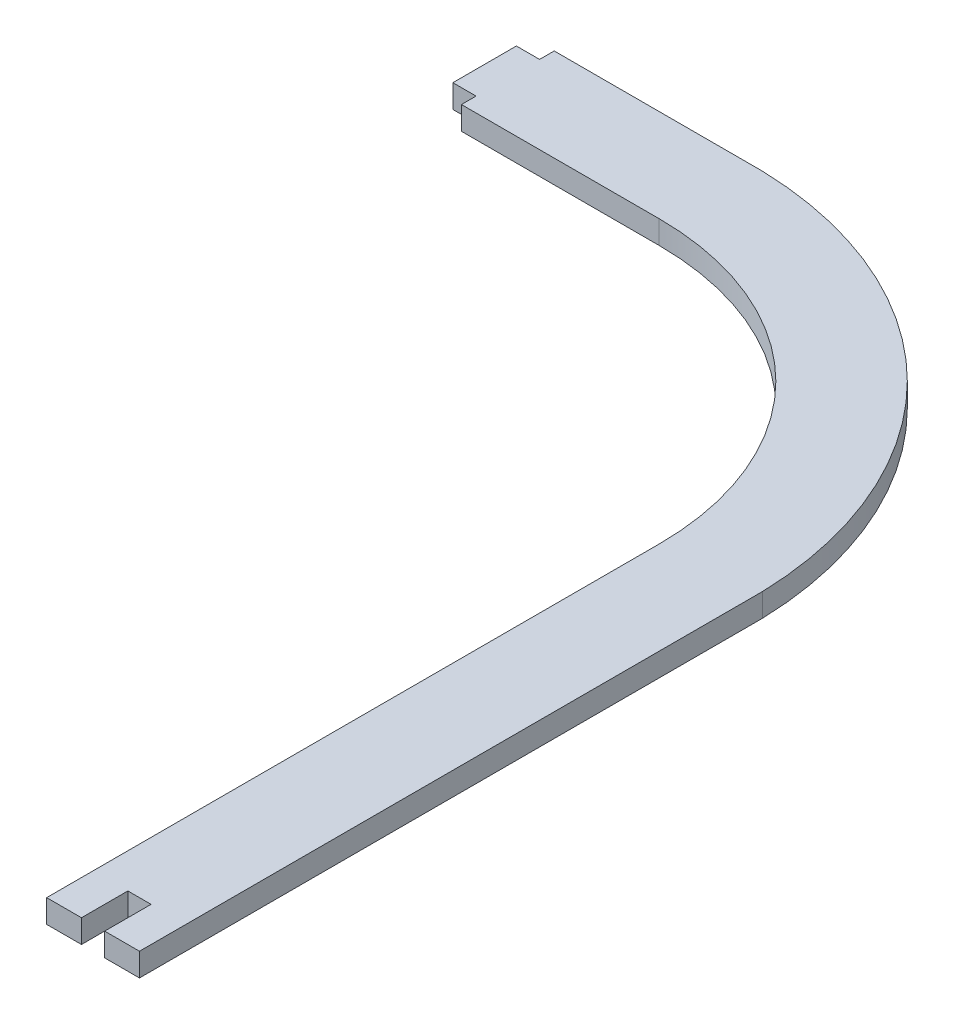
SolidWorks part; units mm, degrees
ref_plane "Alzado" through (0, 0, 0) normal (0, 0, 1) x (1, 0, 0)
ref_plane "Planta" through (0, 0, 0) normal (0, 1, 0) x (1, 0, 0)
ref_plane "Vista lateral" through (0, 0, 0) normal (1, 0, 0) x (0, 0, -1)
sketch "Croquis1" plane through (0, 0, 0) normal (0, 1, 0) x (1, 0, 0)
  line L0 (0, 0) -> (0, 8)
  line L1 (0, 8) -> (3, 8)
  line L2 (3, -2.107) -> (3, -0.2139)
  line L3 (3, 9.893) -> (7.3583, 9.893)
  line L4 (3, 3.893) -> (72.5, 3.893) construction
  line L5 (72.5, 3.893) -> (72.5, -105.737) construction
  line L6 (3, -2.107) -> (7.3583, -2.107)
  line L7 (0, -0.2139) -> (3, -0.2139)
  line L8 (0, 7.7861) -> (0, -0.2139)
  line L9 (3, 8) -> (3, 9.893)
  line L10 (72.5, -111.737) -> (72.5, -117.737)
  line L11 (72.5, -105.737) -> (72.5, -111.737) construction
  line L12 (72.5, -111.737) -> (69.5, -111.737)
  line L13 (69.5, -111.737) -> (69.5, -117.737)
  line L14 (7.3583, -2.107) -> (28.5736, -2.107)
  line L15 (69.5, -117.737) -> (65, -117.737)
  line L16 (72.5, -117.737) -> (77, -117.737)
  line L18 (7.3583, 9.893) -> (29.9532, 9.893)
  line L19 (71, 3.893) -> (28.5736, -38.5334) construction
  line L20 (65, -117.737) -> (65, -38.5334)
  line L21 (71, -105.737) -> (71, 3.893) construction
  line L22 (77, -117.737) -> (77, -37.1537)
  arc A0 (65, -38.5334) -> (28.5736, -2.107) centre (28.5736, -38.5334) ccw
  arc A2 (77, -37.1537) -> (29.9532, 9.893) centre (28.5736, -38.5334) ccw
  dimension "D1" = 8
  dimension "D2" = 3
  dimension "D3" = 6
  dimension "D4" = 69.5
  dimension "D5" = 109.63
  dimension "D7" = 6
  dimension "D8" = 6
  dimension "D12" = 60
extrude "Saliente-Extruir1" add sketch "Croquis1" along normal blind 3 contours L22 A2 L18 L3 L9 L1 L0 L8 L7 L2 L6 L14 A0 L20 L15 L13 L12 L10 L16 region at (1.4906, 0, -3.893)
